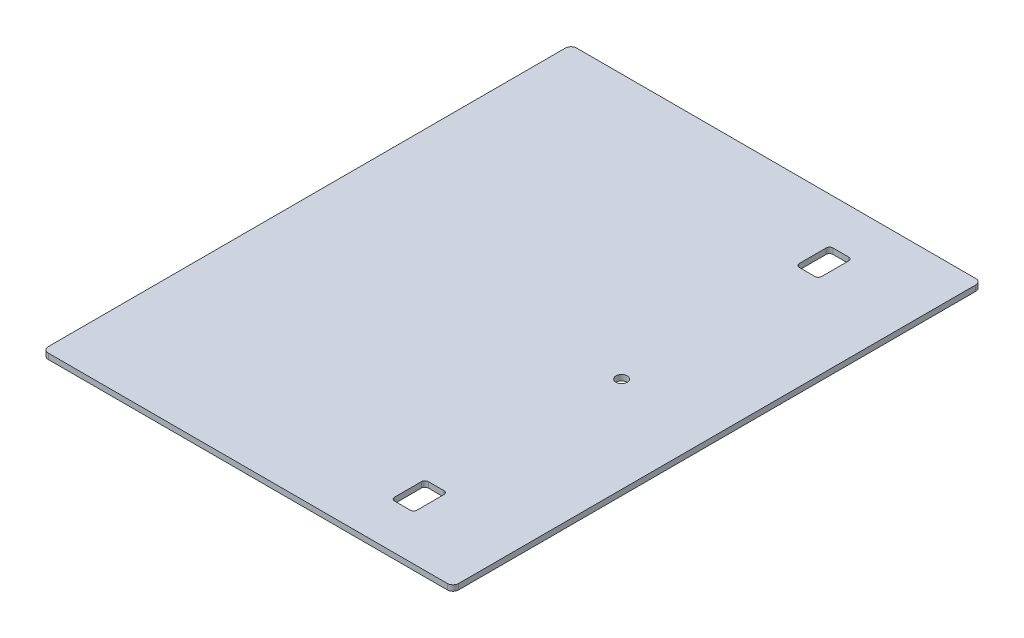
SolidWorks part; units mm, degrees
ref_plane "Front Plane" through (0, 0, 0) normal (0, 0, 1) x (1, 0, 0)
ref_plane "Top Plane" through (0, 0, 0) normal (0, 1, 0) x (1, 0, 0)
ref_plane "Right Plane" through (0, 0, 0) normal (1, 0, 0) x (0, 0, -1)
sketch "Sketch1" plane through (0, 0, 0) normal (0, 1, 0) x (1, 0, 0)
  line L1 (-115.8875, -149.225) -> (115.8875, -149.225)
  line L2 (-115.8875, -149.225) -> (-115.8875, 149.225)
  line L3 (-115.8875, 149.225) -> (115.8875, 149.225)
  line L4 (115.8875, -149.225) -> (115.8875, 149.225)
  line L5 (-115.8875, -149.225) -> (115.8875, 149.225) construction
  line L6 (-115.8875, 149.225) -> (115.8875, -149.225) construction
  point P0 (0, 0)
  dimension "D1" = 298.45
  dimension "D2" = 231.775
extrude "Boss-Extrude1" add sketch "Sketch1" along normal blind 3.175
hole_wizard "1/4 (0.25) Diameter Hole1" positions "Sketch2" profile "Sketch3" hole size "1/4" standard "ANSI Inch" end condition through all
sketch "Sketch2" plane through (0, 3.175, 0) normal (0, 1, 0) x (1, 0, 0)
  line L0 (115.8875, -149.225) -> (115.8875, 149.225) construction
  point P12 (61.9125, 0)
  point P18 (0, 0)
  point P19 (0, 0)
  dimension "D5" = 53.975
sketch "Sketch3" plane through (61.9125, 3.175, 0) normal (1, 0, 0) x (0, 0, 1)
  line L0 (0, 0) -> (0, 3.175)
  line L1 (0, 3.175) -> (3.175, 3.175)
  line L2 (3.175, 3.175) -> (3.175, 0)
  line L5 (3.175, 0) -> (0, 0)
  line L11 (0, -6.35) -> (0, 107.95) construction
  dimension "Thru Hole Dia." = 6.35
  dimension "Thru Hole Depth" = 3.175
fillet "Fillet1" radius 3.175 4 edges at (-115.8875, 1.5875, 149.225) (115.8875, 1.5875, 149.225) (-115.8875, 1.5875, -149.225) (115.8875, 1.5875, -149.225)
sketch "Sketch4" plane through (0, 3.175, 0) normal (0, 1, 0) x (1, 0, 0)
  line L0 (-112.7125, -149.225) -> (112.7125, -149.225) construction
  line L1 (55.5625, -104.775) -> (68.2625, -104.775)
  line L2 (55.5625, -104.775) -> (55.5625, -123.825)
  line L3 (55.5625, -123.825) -> (68.2625, -123.825)
  line L4 (68.2625, -104.775) -> (68.2625, -123.825)
  line L5 (55.5625, 123.825) -> (68.2625, 123.825)
  line L6 (55.5625, 123.825) -> (55.5625, 104.775)
  line L7 (55.5625, 104.775) -> (68.2625, 104.775)
  line L8 (68.2625, 123.825) -> (68.2625, 104.775)
  line L9 (112.7125, 149.225) -> (-112.7125, 149.225) construction
  line L10 (115.8875, -146.05) -> (115.8875, 146.05) construction
  point P14 (61.9125, -123.825)
  dimension "D1" = 25.4
  dimension "D2" = 25.4
  dimension "D3" = 12.7
  dimension "D4" = 19.05
  dimension "D5" = 53.975
extrude "Cut-Extrude1" cut sketch "Sketch4" against normal through all
fillet "Fillet2" radius 1.905 8 edges at (68.2625, 1.5875, 123.825) (68.2625, 1.5875, 104.775) (55.5625, 1.5875, 104.775) (55.5625, 1.5875, 123.825) (55.5625, 1.5875, -104.775) (68.2625, 1.5875, -104.775) (68.2625, 1.5875, -123.825) (55.5625, 1.5875, -123.825)
